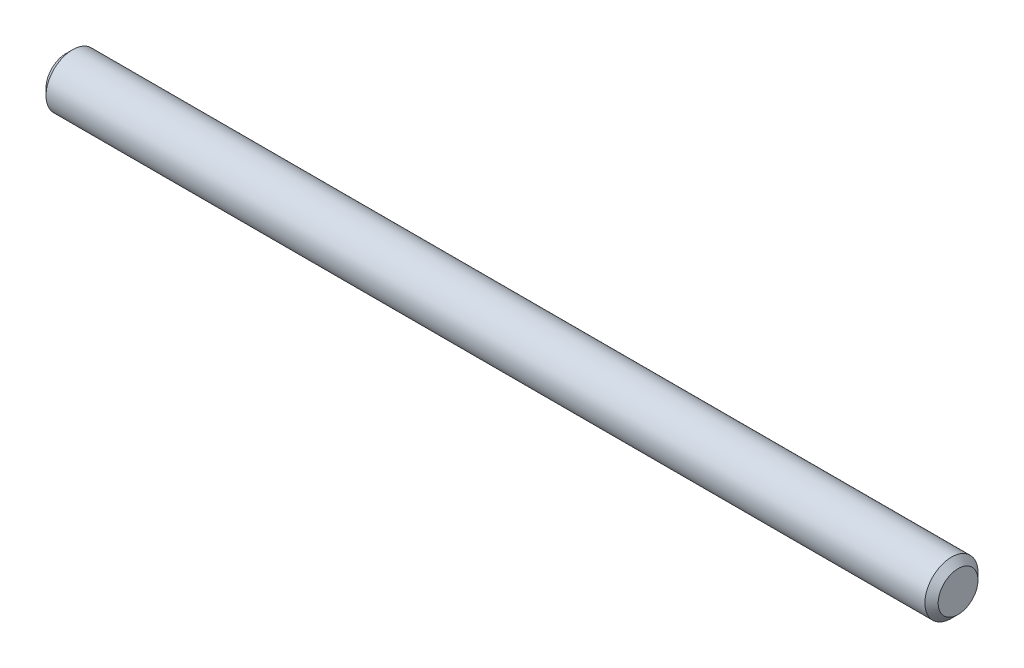
SolidWorks part; units mm, degrees
ref_plane "Front Plane" through (0, 0, 0) normal (0, 0, 1) x (1, 0, 0)
ref_plane "Top Plane" through (0, 0, 0) normal (0, 1, 0) x (1, 0, 0)
ref_plane "Right Plane" through (0, 0, 0) normal (1, 0, 0) x (0, 0, -1)
sketch "Sketch1" plane through (0, 0, 0) normal (0, 0, 1) x (1, 0, 0)
  line L0 (-304.8, 0) -> (304.8, 0) construction
  line L1 (304.8, 4.7625) -> (304.8, -4.7625) construction
  line L2 (-304.8, 4.7625) -> (-304.8, -4.7625) construction
  line L3 (304.8, 4.7625) -> (201.6125, 4.7625) construction
  point P6 (299.2438, -4.7625)
  point P9 (-285.75, 0)
  point P10 (285.75, 0)
  point P11 (-260.35, 0)
  point P12 (260.35, 0)
  dimension "D1" = 5.5562
  dimension "D2" = 19.05
  dimension "D3" = 19.05
  dimension "D4" = 25.4
  dimension "D5" = 25.4
sketch "Sketch2" plane through (0, 0, 0) normal (1, 0, 0) x (0, 0, -1)
  circle A0 centre (0, 0) radius 4.7625
extrude "Boss-Extrude1" add sketch "Sketch2" against normal blind 160
chamfer "Chamfer1" distance 1.1906 angle 45 2 edges at (-160, 0, -4.7625) (0, 0, -4.7625)
sketch "Drawing1" plane through (0, 0, 0) normal (1, 0, 0) x (0, 0, -1)
  circle A0 centre (0, 0) radius 4.7625
sketch "Sketch3" [suppressed] plane through (304.8, 0, 0) normal (1, 0, 0) x (0, 0, -1)
  circle A1 centre (0, 0) radius 4.7625
  circle A2 centre (0, 0) radius 4.7625
  dimension "D1" = 0
curve "Helix/Spiral1" [suppressed] pitch 1.5875 height 104.775 turns 66 parameters "Pitch"=1.5875
sketch "Sketch4" [suppressed] plane through (0, 0, 0) normal (0, 0, 1) x (1, 0, 0)
  line L0 (305.4945, 3.7314) -> (305.4945, 4.7625) construction
  line L1 (305.0977, 4.2469) -> (305.8914, 4.2469) construction
  line L2 (304.2047, 5.7936) -> (305.3953, 3.7314)
  line L3 (306.7844, 5.7936) -> (305.5938, 3.7314)
  line L4 (304.2047, 5.7936) -> (306.7844, 5.7936)
  line L5 (305.3953, 3.7314) -> (305.5938, 3.7314) construction
  line L7 (305.3953, 3.7314) -> (304.8, 4.7625) construction
  line L8 (305.3953, 3.7314) -> (305.5938, 3.7314)
  line L9 (304.8, 4.7625) -> (306.1891, 4.7625) construction
  line L10 (306.1891, 4.7625) -> (305.5938, 3.7314) construction
  point P9 (304.8, 4.7625)
  point P11 (306.1891, 4.7625)
  dimension "D2" = 0.1984
  dimension "D1" = 0.7937
  dimension "D3" = 60
sweep "Cut-Sweep3" [suppressed] cut profiles "Sketch4" path "Helix/Spiral1"
pattern_linear "LPattern1" [suppressed] count 7 spacing 101.6 along (-1, 0, 0) of bodies 102
ref_plane "Plane1" [suppressed] through (-260.35, 0, 0) normal (1, 0, 0) x (0, 0, -1)
ref_plane "Plane2" [suppressed] through (260.35, 0, 0) normal (1, 0, 0) x (0, 0, -1)
split "Split1" [suppressed] bodies to split 103
equation "\"D3@Helix/Spiral1\"=\"Pitch@Helix/Spiral1\"+\"Segment Length@Sketch1\""
equation "\"D1@Chamfer1\" = \"Pitch@Helix/Spiral1\"*.75"
equation "\"D2@Sketch4\"=\"Pitch@Helix/Spiral1\"*.125"
equation "\"D1@Sketch1\" = \"Pitch@Helix/Spiral1\"*3.50"
equation "\"Segment Length@Sketch1\" = \"Pitch@Helix/Spiral1\"*65"
equation "\"D1@LPattern1\"=(\"Length@Sketch1\"/(\"Segment Length@Sketch1\"-\"Pitch@Helix/Spiral1\"))+1"
equation "\"D3@LPattern1\"=\"Segment Length@Sketch1\"-\"Pitch@Helix/Spiral1\""
equation "\"D2@Sketch1\"=\"Thread Diameter@Sketch1\"*2"
equation "\"D3@Sketch1\"=\"Thread Diameter@Sketch1\"*2"
equation "\"D1@Sketch4\"=\"Pitch@Helix/Spiral1\"*.5"
